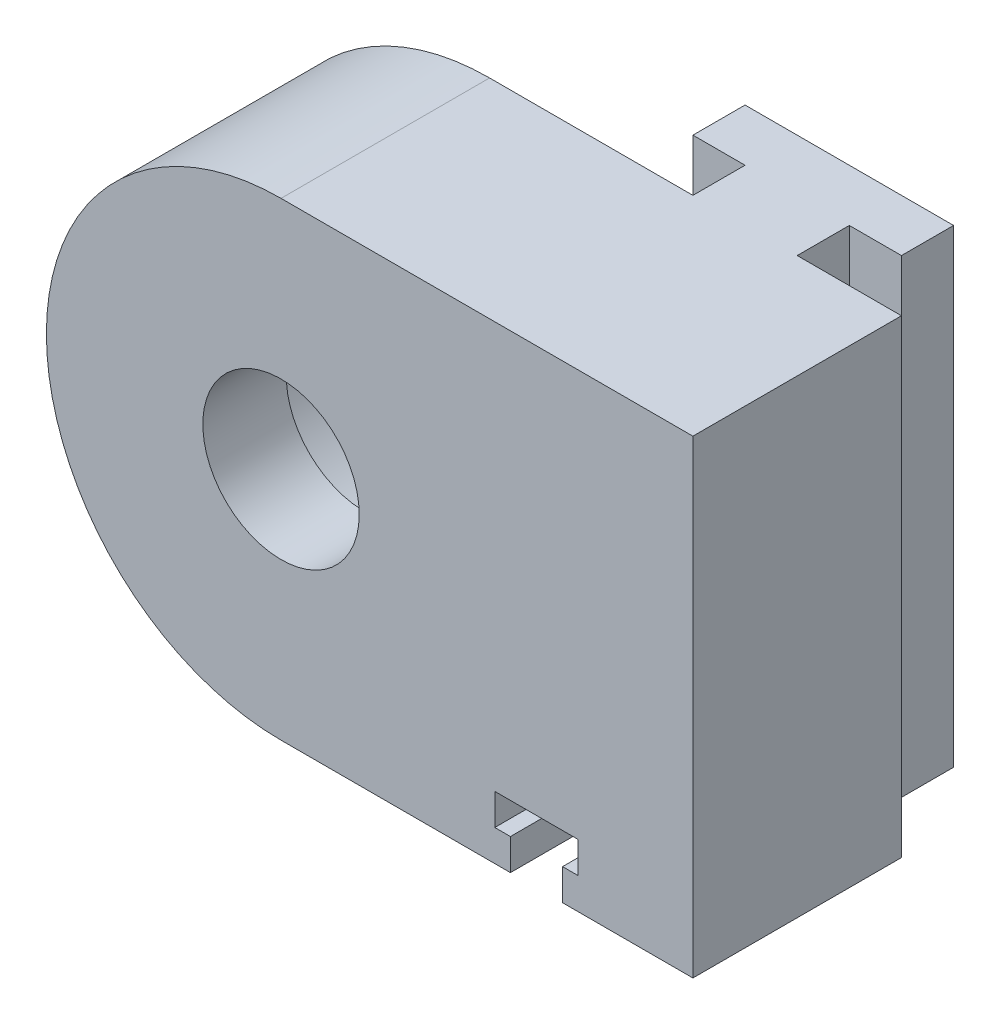
SolidWorks part; units mm, degrees
ref_plane "Plan de face" through (0, 0, 0) normal (0, 0, 1) x (1, 0, 0)
ref_plane "Plan de dessus" through (0, 0, 0) normal (0, 1, 0) x (1, 0, 0)
ref_plane "Plan de droite" through (0, 0, 0) normal (1, 0, 0) x (0, 0, -1)
sketch "Esquisse1" plane through (0, 0, 0) normal (0, 0, 1) x (1, 0, 0)
  line L0 (-634.5081, 20.5) -> (-595.0087, 20.5)
  line L1 (-595.0087, 20.5) -> (-595.0087, -24.5)
  line L2 (-595.0087, -24.5) -> (-634.5081, -24.5)
  line L3 (-666.113, -2) -> (-573.9627, -2) construction
  line L4 (-614.0087, -21.5) -> (-612.5087, -21.5)
  line L5 (-595.0087, -2) -> (-612.0087, -2)
  line L6 (-595.0087, -2) -> (-595.0087, 3.5)
  line L7 (-595.0087, 3.5) -> (-612.0087, 3.5)
  line L8 (-612.0087, -2) -> (-612.0087, 3.5)
  line L9 (-612.5087, -21.5) -> (-612.5087, -24.5)
  line L10 (-606.0087, -18.5) -> (-606.0087, -21.5)
  line L11 (-606.0087, -21.5) -> (-607.5087, -21.5)
  line L12 (-607.5087, -21.5) -> (-607.5087, -24.5)
  line L15 (-614.0087, -18.5) -> (-606.0087, -18.5)
  line L16 (-614.0087, -21.5) -> (-614.0087, -18.5)
  circle A0 centre (-634.5081, -2) radius 7.5
  arc A1 (-634.5081, 20.5) -> (-634.5081, -24.5) centre (-634.5081, -2) ccw
  circle A5 centre (-634.5081, -2) radius 14
  circle A7 centre (-604.0087, 3.5) radius 2
  point P23 (-610.0087, -18.5)
  dimension "D1" = 5.5
  dimension "D3" = 5
  dimension "D4" = 3
  dimension "D5" = 28
  dimension "D6" = 15
  dimension "D8" = 8
  dimension "D9" = 15
  dimension "D11" = 4
  dimension "D12" = 8
  dimension "D13" = 3
  dimension "D2" = 17
  dimension "D7" = 45
  dimension "D10" = 39.4994
extrude "Boss.-Extru.1" add sketch "Esquisse1" along normal mid plane 20 contours L1 L2 A1 L0 | A0
extrude "Enlèv. mat.-Extru.1" cut sketch "Esquisse1<5>" against normal blind 10 and the other way blind 2 contours A5
sketch "Esquisse1<5>" plane through (0, 0, 0) normal (0, 0, 1) x (1, 0, 0) same geometry as "Esquisse1"
sketch "Esquisse2" plane through (0, 20.5, 0) normal (0, 1, 0) x (1, 0, 0)
  line L0 (-605.0087, 10) -> (-605.0087, 15)
  line L1 (-634.5081, 10) -> (-595.0087, 10) construction
  line L2 (-605.0087, 15) -> (-600.0087, 15)
  line L3 (-600.0087, 15) -> (-600.0087, 20)
  line L4 (-600.0087, 20) -> (-620.0087, 20)
  line L5 (-620.0087, 20) -> (-620.0087, 15)
  line L6 (-620.0087, 15) -> (-615.0087, 15)
  line L7 (-615.0087, 15) -> (-615.0087, 10)
  line L8 (-615.0087, 10) -> (-605.0087, 10)
  line L9 (-595.0087, -10) -> (-595.0087, 10) construction
  dimension "D1" = 20
  dimension "D2" = 5
  dimension "D3" = 10
  dimension "D4" = 10
  dimension "D5" = 5
extrude "Boss.-Extru.2" add sketch "Esquisse2" against normal blind 45
extrude "Enlèv. mat.-Extru.2" cut sketch "Esquisse1<7>" along normal through all both and the other way through all contours L2 L15 L16 region at (-610.0087, -21.1538, 0)
sketch "Esquisse1<7>" plane through (0, 0, 0) normal (0, 0, 1) x (1, 0, 0) same geometry as "Esquisse1"
